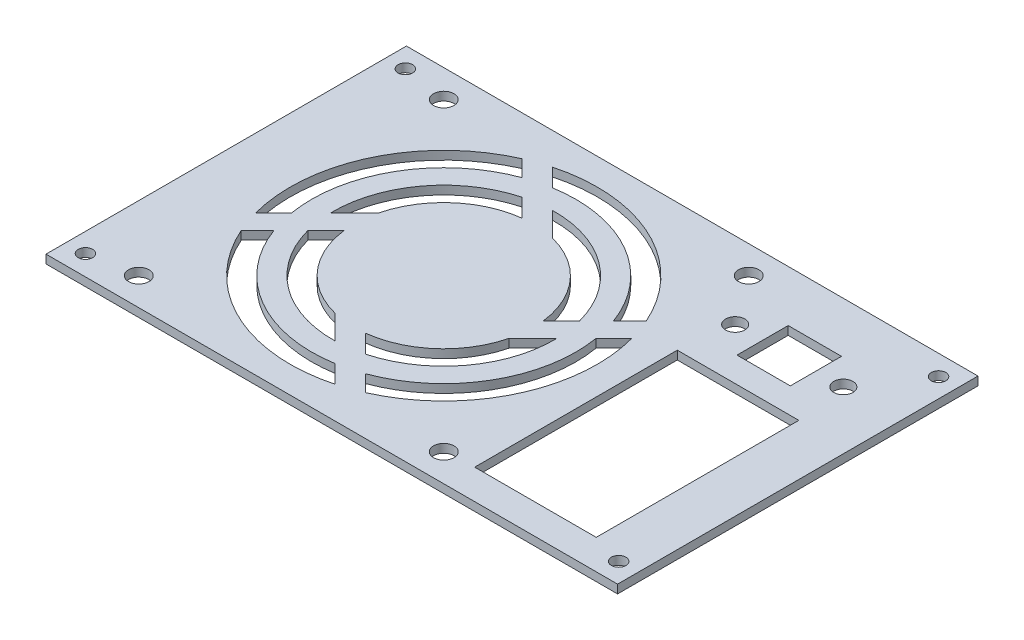
SolidWorks part; units mm, degrees
material "Thornel Mat VMA"
ref_plane "Front Plane" through (0, 0, 0) normal (0, 0, 1) x (1, 0, 0)
ref_plane "Top Plane" through (0, 0, 0) normal (0, 1, 0) x (1, 0, 0)
ref_plane "Right Plane" through (0, 0, 0) normal (1, 0, 0) x (0, 0, -1)
sketch "Sketch1" plane through (0, 0, 0) normal (0, 1, 0) x (1, 0, 0)
  line L1 (0, 0) -> (134, 0)
  line L2 (0, 0) -> (0, 84.5)
  line L3 (0, 84.5) -> (134, 84.5)
  line L4 (134, 0) -> (134, 84.5)
  dimension "D1" = 134
  dimension "D2" = 84.5
extrude "Boss-Extrude1" add sketch "Sketch1" along normal blind 2
sketch "Sketch2" plane through (0, 2, 0) normal (0, 1, 0) x (1, 0, 0)
  line L0 (67, 42.25) -> (67, 84.5) construction
  line L2 (134, 84.5) -> (0, 84.5) construction
  line L3 (129.5, 79.75) -> (4.5, 79.75) construction
  line L4 (129.5, 79.75) -> (129.5, 4.75) construction
  line L5 (129.5, 4.75) -> (4.5, 4.75) construction
  line L6 (4.5, 79.75) -> (4.5, 4.75) construction
  line L7 (129.5, 79.75) -> (4.5, 4.75) construction
  line L8 (129.5, 4.75) -> (4.5, 79.75) construction
  line L11 (0, 0) -> (134, 0) construction
  line L13 (134, 0) -> (134, 84.5) construction
  line L14 (67, 42.25) -> (134, 42.25) construction
  line L15 (67, 42.25) -> (0, 42.25) construction
  line L16 (0, 84.5) -> (0, 0) construction
  line L17 (67, 42.25) -> (67, 0) construction
  circle A0 centre (4.5, 4.75) radius 1.6
  circle A1 centre (4.5, 79.75) radius 1.6
  circle A2 centre (129.5, 79.75) radius 1.6
  circle A3 centre (129.5, 4.75) radius 1.6
  point P8 (67, 42.25)
  dimension "D1" = 3.2
  dimension "D2" = 125
  dimension "D3" = 75
hole_wizard "M3 Clearance Hole1" positions "Sketch4" profile "Sketch3" hole size "M3" standard "ANSI Metric"
sketch "Sketch4" plane through (0, 2, 0) normal (0, 1, 0) x (1, 0, 0)
  point P0 (4.5, 79.75)
  point P3 (129.5, 79.75)
  point P6 (129.5, 4.75)
  point P9 (4.5, 4.75)
sketch "Sketch3" plane through (4.5, 2, -79.75) normal (1, 0, 0) x (0, 0, 1)
  line L0 (0, 0) -> (0, 6.0215)
  line L1 (0, 6.0215) -> (1.7, 5)
  line L2 (1.7, 5) -> (1.7, 0)
  line L5 (1.7, 0) -> (0, 0)
  line L10 (0, 6.0215) -> (-1.7, 5) construction
  line L11 (0, -6.35) -> (0, 107.95) construction
  dimension "Hole Dia." = 3.4
  dimension "Hole Depth" = 5
  dimension "Drill Angle" = 118
sketch "Sketch5" plane through (0, 2, 0) normal (0, 1, 0) x (1, 0, 0)
  line L0 (0, 42.25) -> (51, 42.25) construction
  line L1 (15.25, 78) -> (86.75, 78) construction
  line L2 (15.25, 78) -> (15.25, 6.5) construction
  line L3 (15.25, 6.5) -> (86.75, 6.5) construction
  line L4 (86.75, 78) -> (86.75, 6.5) construction
  line L5 (15.25, 78) -> (86.75, 6.5) construction
  line L6 (15.25, 6.5) -> (86.75, 78) construction
  line L7 (0, 84.5) -> (0, 0) construction
  point P0 (51, 42.25)
  dimension "D1" = 71.5
  dimension "D2" = 51
hole_wizard "M4 Clearance Hole1" positions "Sketch7" profile "Sketch8" hole size "M4" standard "ANSI Metric" end condition through all
sketch "Sketch7" plane through (0, 2, 0) normal (0, 1, 0) x (1, 0, 0)
  point P0 (15.25, 78)
  point P3 (86.75, 78)
  point P6 (86.75, 6.5)
  point P9 (15.25, 6.5)
sketch "Sketch8" plane through (15.25, 2, -78) normal (1, 0, 0) x (0, 0, 1)
  line L0 (0, 0) -> (0, 2)
  line L1 (0, 2) -> (2.4, 2)
  line L2 (2.4, 2) -> (2.4, 0)
  line L5 (2.4, 0) -> (0, 0)
  line L11 (0, -6.35) -> (0, 107.95) construction
  dimension "Thru Hole Dia." = 4.8
  dimension "Thru Hole Depth" = 2
sketch "Sketch9" plane through (0, 2, 0) normal (0, 1, 0) x (1, 0, 0)
  line L0 (107.75, 30.75) -> (107.75, 66.5) construction
  line L1 (93.5, 7) -> (122, 7)
  line L2 (93.5, 7) -> (93.5, 54.5)
  line L3 (93.5, 54.5) -> (122, 54.5)
  line L4 (122, 7) -> (122, 54.5)
  line L5 (93.5, 7) -> (122, 54.5) construction
  line L6 (93.5, 54.5) -> (122, 7) construction
  line L7 (0, 0) -> (134, 0) construction
  line L8 (101.5, 72.5) -> (114, 72.5)
  line L9 (101.5, 72.5) -> (101.5, 60.5)
  line L10 (101.5, 60.5) -> (114, 60.5)
  line L11 (114, 72.5) -> (114, 60.5)
  line L12 (101.5, 72.5) -> (114, 60.5) construction
  line L13 (101.5, 60.5) -> (114, 72.5) construction
  line L14 (134, 0) -> (134, 84.5) construction
  point P0 (107.75, 30.75)
  dimension "D1" = 28.5
  dimension "D2" = 47.5
  dimension "D3" = 12
  dimension "D4" = 12.5
  dimension "D5" = 6
  dimension "D6" = 7
  dimension "D7" = 12
extrude "Cut-Extrude1" cut sketch "Sketch9" against normal through all
sketch "Sketch10" plane through (0, 2, 0) normal (0, 1, 0) x (1, 0, 0)
  line L0 (107.75, 72.5) -> (107.75, 60.5) construction
  line L1 (114, 72.5) -> (101.5, 72.5) construction
  line L2 (101.5, 60.5) -> (114, 60.5) construction
  line L3 (95.075, 66.5) -> (120.425, 66.5) construction
  point P8 (107.75, 66.5)
  dimension "D1" = 25.35
hole_wizard "M4 Clearance Hole2" positions "Sketch12" profile "Sketch11" hole size "M4" standard "ANSI Metric" end condition through all
sketch "Sketch12" plane through (0, 2, 0) normal (0, 1, 0) x (1, 0, 0)
  point P0 (95.075, 66.5)
  point P3 (120.425, 66.5)
sketch "Sketch11" plane through (95.075, 2, -66.5) normal (1, 0, 0) x (0, 0, 1)
  line L0 (0, 0) -> (0, 2)
  line L1 (0, 2) -> (2.25, 2)
  line L2 (2.25, 2) -> (2.25, 0)
  line L5 (2.25, 0) -> (0, 0)
  line L11 (0, -6.35) -> (0, 107.95) construction
  dimension "Thru Hole Dia." = 4.5
  dimension "Thru Hole Depth" = 2
sketch "Sketch14" plane through (0, 2, 0) normal (0, 1, 0) x (1, 0, 0)
  line L0 (15.25, 78) -> (86.75, 6.5) construction
  line L1 (63.0208, 30.2292) -> (87.8402, 55.0485) construction
  line L2 (39.0036, 30.2536) -> (63.8229, 5.4343) construction
  line L3 (39.028, 54.2708) -> (14.2087, 29.4515) construction
  line L4 (63.0452, 54.2464) -> (38.2259, 79.0657) construction
  line L5 (71.8543, 44.7195) -> (76.1141, 48.9793)
  line L6 (41.6825, 77.0233) -> (45.8814, 72.8245)
  line L7 (50.4614, 68.2444) -> (56.0794, 62.6265)
  line L8 (80.0921, 52.9574) -> (83.9305, 56.7958)
  line L9 (53.4695, 21.3957) -> (57.7293, 17.1359)
  line L10 (76.9944, 42.7886) -> (71.3765, 37.1706)
  line L11 (85.7733, 51.5675) -> (81.5745, 47.3686)
  line L12 (61.7074, 13.1579) -> (65.5458, 9.3195)
  line L13 (30.1457, 39.7805) -> (25.8859, 35.5207)
  line L14 (51.5386, 16.2556) -> (45.9206, 21.8735)
  line L15 (60.3175, 7.4767) -> (56.1186, 11.6755)
  line L16 (21.9079, 31.5426) -> (18.0695, 27.7042)
  line L17 (48.5305, 63.1043) -> (44.2707, 67.3641)
  line L18 (25.0056, 41.7114) -> (30.6235, 47.3294)
  line L19 (16.2267, 32.9325) -> (20.4255, 37.1314)
  line L20 (40.2926, 71.3421) -> (36.4542, 75.1805)
  circle A0 centre (51, 42.25) radius 39 construction
  circle A1 centre (51, 42.25) radius 17 construction
  arc A2 (83.9305, 56.7958) -> (41.6825, 77.0233) centre (51, 42.25) ccw
  arc A3 (80.0921, 52.9574) -> (45.8814, 72.8245) centre (51, 42.25) ccw
  arc A4 (76.1141, 48.9793) -> (50.4614, 68.2444) centre (51, 42.25) ccw
  arc A5 (71.8543, 44.7195) -> (56.0794, 62.6265) centre (51, 42.25) ccw
  arc A6 (53.4695, 21.3957) -> (71.3765, 37.1706) centre (51, 42.25) ccw
  arc A7 (57.7293, 17.1359) -> (76.9944, 42.7886) centre (51, 42.25) ccw
  arc A8 (61.7074, 13.1579) -> (81.5745, 47.3686) centre (51, 42.25) ccw
  arc A9 (65.5458, 9.3195) -> (85.7733, 51.5675) centre (51, 42.25) ccw
  arc A10 (30.1457, 39.7805) -> (45.9206, 21.8735) centre (51, 42.25) ccw
  arc A11 (25.8859, 35.5207) -> (51.5386, 16.2556) centre (51, 42.25) ccw
  arc A12 (21.9079, 31.5426) -> (56.1186, 11.6755) centre (51, 42.25) ccw
  arc A13 (18.0695, 27.7042) -> (60.3175, 7.4767) centre (51, 42.25) ccw
  arc A14 (48.5305, 63.1043) -> (30.6235, 47.3294) centre (51, 42.25) ccw
  arc A15 (44.2707, 67.3641) -> (25.0056, 41.7114) centre (51, 42.25) ccw
  arc A16 (40.2926, 71.3421) -> (20.4255, 37.1314) centre (51, 42.25) ccw
  arc A17 (36.4542, 75.1805) -> (16.2267, 32.9325) centre (51, 42.25) ccw
  point P18 (51.0244, 42.25)
  point P51 (51, 42.25)
  dimension "D1" = 34
  dimension "D2" = 78
  dimension "D6" = 5
  dimension "D7" = 5
  dimension "D8" = 5
  dimension "D9" = 4
  dimension "D4" = 1
  dimension "D5" = 4
  dimension "D3" = 4
  dimension "D10" = 4
extrude "Cut-Extrude5" cut sketch "Sketch14" against normal through all
